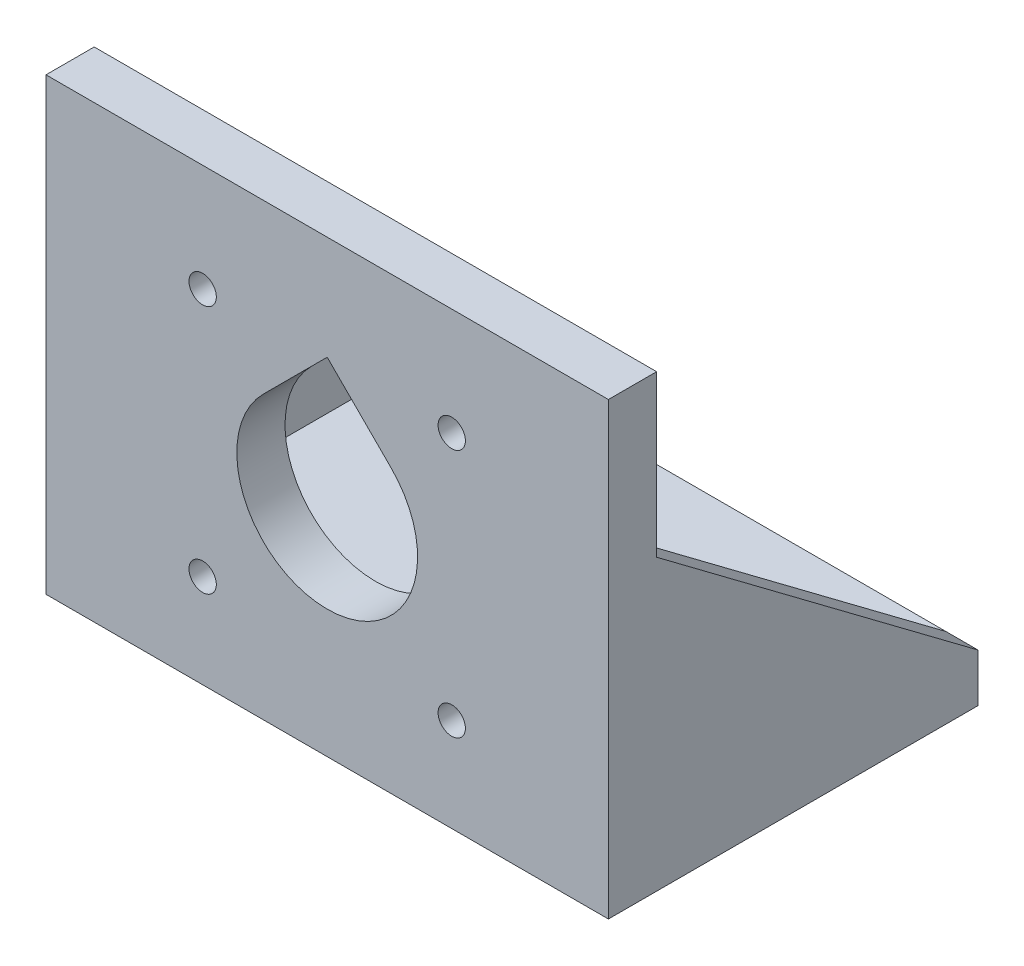
SolidWorks part; units mm, degrees
ref_plane "Спереди" through (0, 0, 0) normal (0, 0, 1) x (1, 0, 0)
ref_plane "Сверху" through (0, 0, 0) normal (0, 1, 0) x (1, 0, 0)
ref_plane "Справа" through (0, 0, 0) normal (1, 0, 0) x (0, 0, -1)
other "Configuration Table"
sketch "01_Пластина_эскиз" plane through (0, 0, 0) normal (0, 0, 1) x (1, 0, 0)
  line L1 (0, 0) -> (70, 0)
  line L2 (0, 0) -> (0, 56)
  line L3 (0, 56) -> (70, 56)
  line L4 (70, 0) -> (70, 56)
  dimension "D1" = 70
  dimension "D2" = 56
extrude "01_Передняя_пластина" add sketch "01_Пластина_эскиз" along normal blind 6
sketch "02_Полка_эскиз" plane through (0, 0, 0) normal (0, 1, 0) x (1, 0, 0)
  line L1 (0, 40) -> (70, 40)
  line L2 (0, 40) -> (0, -6)
  line L3 (0, -6) -> (70, -6)
  line L4 (70, 40) -> (70, -6)
  dimension "D1" = 70
  dimension "D2" = 46
  dimension "D3" = 6
  dimension "D4" = 6
extrude "02_Полка" add sketch "02_Полка_эскиз" along normal blind 6
sketch "03_Косынка_левая_эскиз" plane through (0, 0, 0) normal (1, 0, 0) x (0, 0, -1)
  line L0 (40, 6) -> (0, 6)
  line L1 (0, 6) -> (0, 36)
  line L2 (0, 36) -> (40, 6)
  dimension "D3" = 6
  dimension "D1" = 40
  dimension "D2" = 30
extrude "03_Косынка_левая" add sketch "03_Косынка_левая_эскиз" along normal blind 4
sketch "04_Косынка_правая_эскиз" plane through (0, 0, 0) normal (1, 0, 0) x (0, 0, -1)
  line L0 (40, 6) -> (0, 6)
  line L1 (0, 6) -> (0, 36)
  line L2 (0, 36) -> (40, 6)
  dimension "D3" = 6
  dimension "D1" = 40
  dimension "D2" = 30
extrude "04_Косынка_правая" add sketch "04_Косынка_правая_эскиз" along normal blind 4 from offset 66
sketch "05_Мотор_передний_фланец_эскиз" plane through (0, 0, 0) normal (0, 0, 1) x (1, 0, 0)
  line L0 (4, 6) -> (66, 6) construction
  circle A0 centre (35, 27.15) radius 11.25
  circle A1 centre (19.5, 11.65) radius 1.7
  circle A2 centre (19.5, 42.65) radius 1.7
  circle A3 centre (50.5, 11.65) radius 1.7
  circle A4 centre (50.5, 42.65) radius 1.7
  dimension "D1" = 3.4
  dimension "D2" = 3.4
  dimension "D3" = 3.4
  dimension "D4" = 3.4
  dimension "D5" = 22.5
  dimension "D6" = 15.5
  dimension "D7" = 31
  dimension "D8" = 15.5
  dimension "D9" = 31
  dimension "D10" = 35
  dimension "D11" = 21.15
extrude "05_Буртик_и_4_отверстия_М3" cut sketch "05_Мотор_передний_фланец_эскиз" against normal through all and the other way through all
sketch "06_Свод_45град_эскиз" plane through (0, 0, 0) normal (0, 0, 1) x (1, 0, 0)
  line L0 (27.045, 35.105) -> (42.955, 35.105)
  line L1 (42.955, 35.105) -> (35, 43.0599)
  line L2 (35, 43.0599) -> (27.045, 35.105)
  circle A0 centre (35, 27.15) radius 11.25 construction
  point P4 (0, 0)
  dimension "D1" = 7.955
  dimension "D2" = 15.9099
  dimension "D3" = 7.955
  dimension "D4" = 35
extrude "06_Свод_отверстия_для_печати" cut sketch "06_Свод_45град_эскиз" against normal through all and the other way through all
sketch "07_Крепление_полки_эскиз" plane through (0, 0, 0) normal (0, 1, 0) x (1, 0, 0)
  circle A0 centre (8.5, 12) radius 2.25
  circle A1 centre (8.5, 30) radius 2.25
  circle A2 centre (61.5, 12) radius 2.25
  circle A3 centre (61.5, 30) radius 2.25
  dimension "D1" = 4.5
  dimension "D2" = 4.5
  dimension "D3" = 4.5
  dimension "D4" = 4.5
  dimension "D5" = 53
  dimension "D6" = 18
  dimension "D7" = 8.5
  dimension "D8" = 12
extrude "07_4_отверстия_М4" cut sketch "07_Крепление_полки_эскиз" against normal through all and the other way through all
equation "\"Ширина\"= 70"
equation "\"Высота пластины\"= 56"
equation "\"Толщина стенок\"= 6"
equation "\"Длина полки\"= 40"
equation "\"Толщина косынки\"= 4"
equation "\"Высота косынки\"= 30"
equation "\"Высота оси\"= 30"
equation "\"Шаг М3 ПРЕДВ\"= 31"
equation "\"Отверстие буртика\"= 22.5"
equation "\"Отверстия М3\"= 3.4"
equation "\"Отверстия М4\"= 4.5"
equation "\"Отступ М4 сбоку\"= 8.5"
equation "\"Ближний ряд М4\"= 12"
equation "\"Отступ М4 сзади\"= 10"
equation "\"D1@01_Пластина_эскиз\" = \"Ширина\""
equation "\"D2@01_Пластина_эскиз\" = \"Высота пластины\""
equation "\"D1@01_Передняя_пластина\" = \"Толщина стенок\""
equation "\"D1@02_Полка_эскиз\" = \"Ширина\""
equation "\"D2@02_Полка_эскиз\" = \"Длина полки\" + \"Толщина стенок\""
equation "\"D1@02_Полка\" = \"Толщина стенок\""
equation "\"D1@03_Косынка_левая_эскиз\" = \"Длина полки\""
equation "\"D2@03_Косынка_левая_эскиз\" = \"Высота косынки\""
equation "\"D1@03_Косынка_левая\" = \"Толщина косынки\""
equation "\"D1@04_Косынка_правая_эскиз\" = \"Длина полки\""
equation "\"D2@04_Косынка_правая_эскиз\" = \"Высота косынки\""
equation "\"D1@04_Косынка_правая\" = \"Толщина косынки\""
equation "\"D19@04_Косынка_правая\" = \"Ширина\" - \"Толщина косынки\""
equation "\"D1@05_Мотор_передний_фланец_эскиз\" = \"Отверстия М3\""
equation "\"D2@05_Мотор_передний_фланец_эскиз\" = \"Отверстия М3\""
equation "\"D3@05_Мотор_передний_фланец_эскиз\" = \"Отверстия М3\""
equation "\"D4@05_Мотор_передний_фланец_эскиз\" = \"Отверстия М3\""
equation "\"D5@05_Мотор_передний_фланец_эскиз\" = \"Отверстие буртика\""
equation "\"D6@05_Мотор_передний_фланец_эскиз\" = \"Шаг М3 ПРЕДВ\" / 2"
equation "\"D7@05_Мотор_передний_фланец_эскиз\" = \"Шаг М3 ПРЕДВ\""
equation "\"D8@05_Мотор_передний_фланец_эскиз\" = \"Шаг М3 ПРЕДВ\" / 2"
equation "\"D9@05_Мотор_передний_фланец_эскиз\" = \"Шаг М3 ПРЕДВ\""
equation "\"D1@07_Крепление_полки_эскиз\" = \"Отверстия М4\""
equation "\"D2@07_Крепление_полки_эскиз\" = \"Отверстия М4\""
equation "\"D3@07_Крепление_полки_эскиз\" = \"Отверстия М4\""
equation "\"D4@07_Крепление_полки_эскиз\" = \"Отверстия М4\""
equation "\"D5@07_Крепление_полки_эскиз\" = \"Ширина\" - 2 * \"Отступ М4 сбоку\""
equation "\"D3@02_Полка_эскиз\" = \"Толщина стенок\""
equation "\"D3@03_Косынка_левая_эскиз\" = \"Толщина стенок\""
equation "\"D3@04_Косынка_правая_эскиз\" = \"Толщина стенок\""
equation "\"D10@05_Мотор_передний_фланец_эскиз\" = \"Ширина\" / 2"
equation "\"D1@06_Свод_45град_эскиз\" = \"Отверстие буртика\" / (2 * SQR(2))"
equation "\"D2@06_Свод_45град_эскиз\" = \"Отверстие буртика\" / SQR(2)"
equation "\"D3@06_Свод_45град_эскиз\" = \"Отверстие буртика\" / (2 * SQR(2))"
equation "\"D4@06_Свод_45град_эскиз\" = \"Ширина\" / 2"
equation "\"D6@07_Крепление_полки_эскиз\" = \"Длина полки\" - \"Ближний ряд М4\" - \"Отступ М4 сзади\""
equation "\"D7@07_Крепление_полки_эскиз\" = \"Отступ М4 сбоку\""
equation "\"D8@07_Крепление_полки_эскиз\" = \"Ближний ряд М4\""
